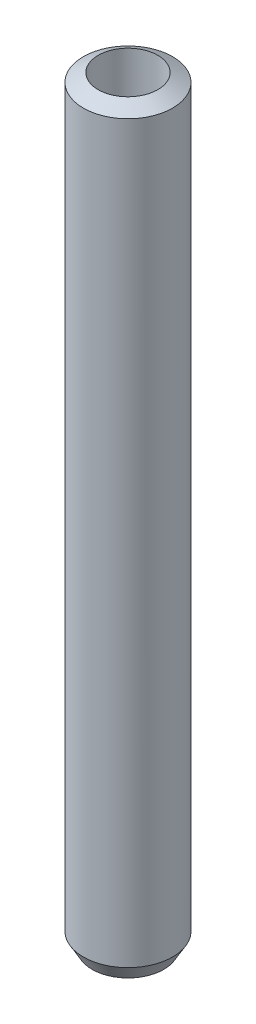
SolidWorks part; units mm, degrees
ref_plane "Front Plane" through (0, 0, 0) normal (0, 0, 1) x (1, 0, 0)
ref_plane "Top Plane" through (0, 0, 0) normal (0, 1, 0) x (1, 0, 0)
ref_plane "Right Plane" through (0, 0, 0) normal (1, 0, 0) x (0, 0, -1)
sketch "Sketch1" plane through (0, 0, 0) normal (0, 1, 0) x (1, 0, 0)
  circle A0 centre (0, 0) radius 15
  dimension "SHAFT_OD" = 30
extrude "Boss-Extrude1" add sketch "Sketch1" along normal blind 255.2472
sketch "Sketch2" plane through (0, 0, 0) normal (0, 1, 0) x (1, 0, 0)
  circle A0 centre (0, 0) radius 10.0218
  dimension "BORE_D" = 20.0436
extrude "Cut-Extrude1" cut sketch "Sketch2" along normal through all
chamfer "Chamfer1" distance 2.9385 angle 60 2 edges at (0, 255.2472, 15) (0, 0, 15) first distance on face at (0, 255.2472, 15) first distance on face at (0, 0, 10.0218)
